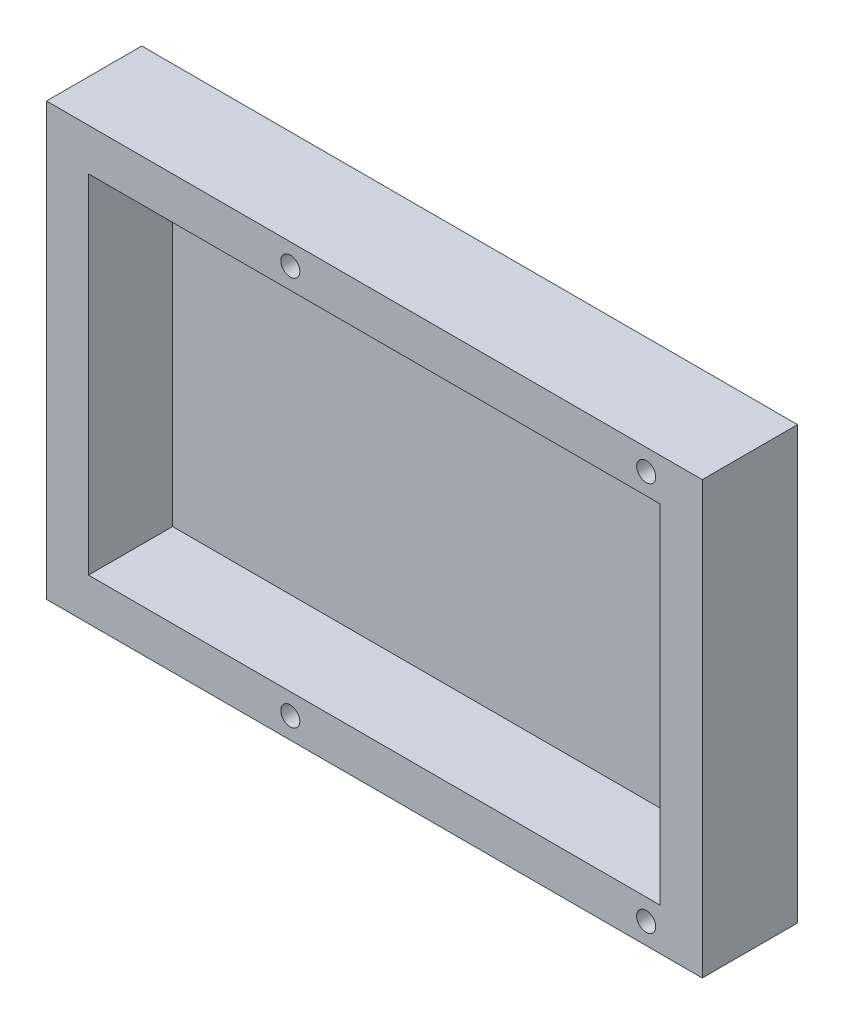
SolidWorks part; units mm, degrees
material "ABS"
ref_plane "Front" through (0, 0, 0) normal (0, 0, 1) x (1, 0, 0)
ref_plane "Top" through (0, 0, 0) normal (0, 1, 0) x (1, 0, 0)
ref_plane "Right" through (0, 0, 0) normal (1, 0, 0) x (0, 0, -1)
sketch "ｽｹｯﾁ1" plane through (0, 0, 0) normal (0, 0, 1) x (1, 0, 0)
  line L1 (58.5, 38.5) -> (-58.5, 38.5)
  line L2 (58.5, 38.5) -> (58.5, -38.5)
  line L3 (58.5, -38.5) -> (-58.5, -38.5)
  line L4 (-58.5, 38.5) -> (-58.5, -38.5)
  line L5 (58.5, 38.5) -> (-58.5, -38.5) construction
  line L6 (58.5, -38.5) -> (-58.5, 38.5) construction
  point P0 (0, 0)
  dimension "D1" = 117
  dimension "D2" = 77
extrude "ﾎﾞｽ - 押し出し1" add sketch "ｽｹｯﾁ1" along normal blind 17
sketch "ｽｹｯﾁ2" plane through (0, 0, 17) normal (0, 0, 1) x (1, 0, 0)
  line L1 (51, 31) -> (-51, 31)
  line L2 (51, 31) -> (51, -31)
  line L3 (51, -31) -> (-51, -31)
  line L4 (-51, 31) -> (-51, -31)
  line L5 (51, 31) -> (-51, -31) construction
  line L6 (51, -31) -> (-51, 31) construction
  point P0 (0, 0)
  dimension "D1" = 102
  dimension "D2" = 62
extrude "ｶｯﾄ - 押し出し1" cut sketch "ｽｹｯﾁ2" against normal offset from surface (15 mm away) 2 up to face at (0, 0, 0)
sketch "ｽｹｯﾁ4" plane through (0, 0, 0) normal (0, 0, -1) x (-1, 0, 0)
  line L0 (-58.5, -38.5) -> (-58.5, 38.5) construction
  line L1 (-58.5, 38.5) -> (58.5, 38.5) construction
  line L2 (58.5, -38.5) -> (-58.5, -38.5) construction
  circle A0 centre (15, 34.75) radius 1.7
  circle A1 centre (15, -34.75) radius 1.7
  circle A2 centre (-48.5, -34.75) radius 1.7
  circle A3 centre (-48.5, 34.75) radius 1.7
  dimension "D1" = 3.4
  dimension "D2" = 10
  dimension "D3" = 3.75
  dimension "D4" = 3.75
  dimension "D5" = 73.5
extrude "ｶｯﾄ - 押し出し2" cut sketch "ｽｹｯﾁ4" against normal through all
